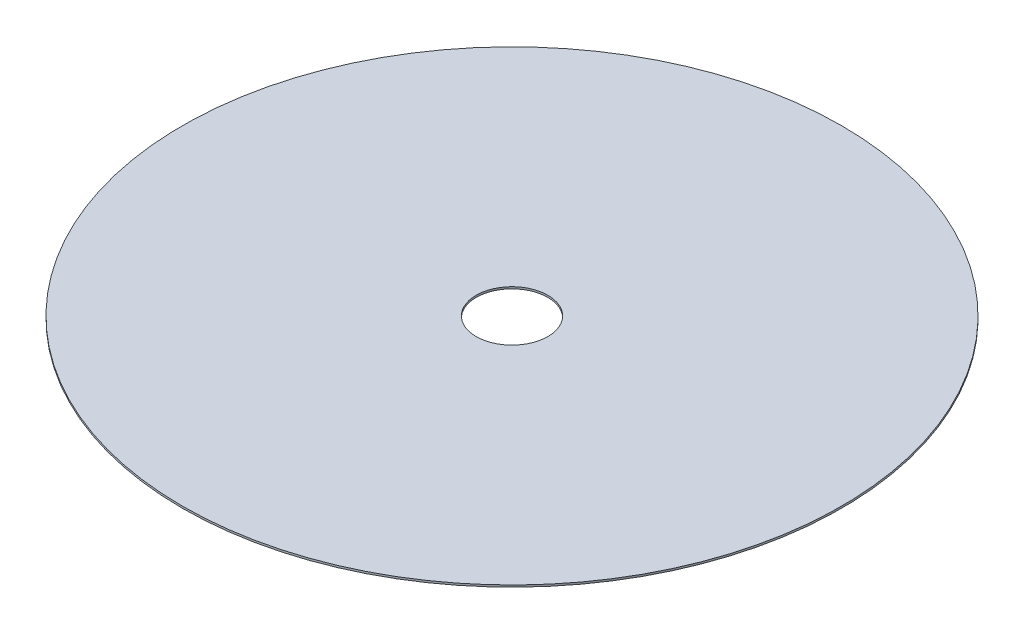
SolidWorks part; units mm, degrees
material "Stainless Steel (ferritic)"
ref_plane "Front Plane" through (0, 0, 0) normal (0, 0, 1) x (1, 0, 0)
ref_plane "Top Plane" through (0, 0, 0) normal (0, 1, 0) x (1, 0, 0)
ref_plane "Right Plane" through (0, 0, 0) normal (1, 0, 0) x (0, 0, -1)
ref_axis "X-Axis" through (-88.99, 0, 0) along (1, 0, 0)
ref_axis "Y-Axis" through (0, 55, 0) along (0, -1, 0)
ref_axis "Z-Axis" through (0, 0, -88.99) along (0, 0, 1)
sketch "Sketch1" plane through (0, 0, 0) normal (0, 1, 0) x (1, 0, 0)
  line L0 (61.9356, 340.2657) -> (628.6023, 340.2657) construction
  circle A0 centre (0, 0) radius 43.815
  circle A1 centre (0, 0) radius 4.7625
  dimension "D1" = 9.525
  dimension "D2" = 87.63
extrude "Boss-Extrude2" add sketch "Sketch1" along normal blind 0.254
